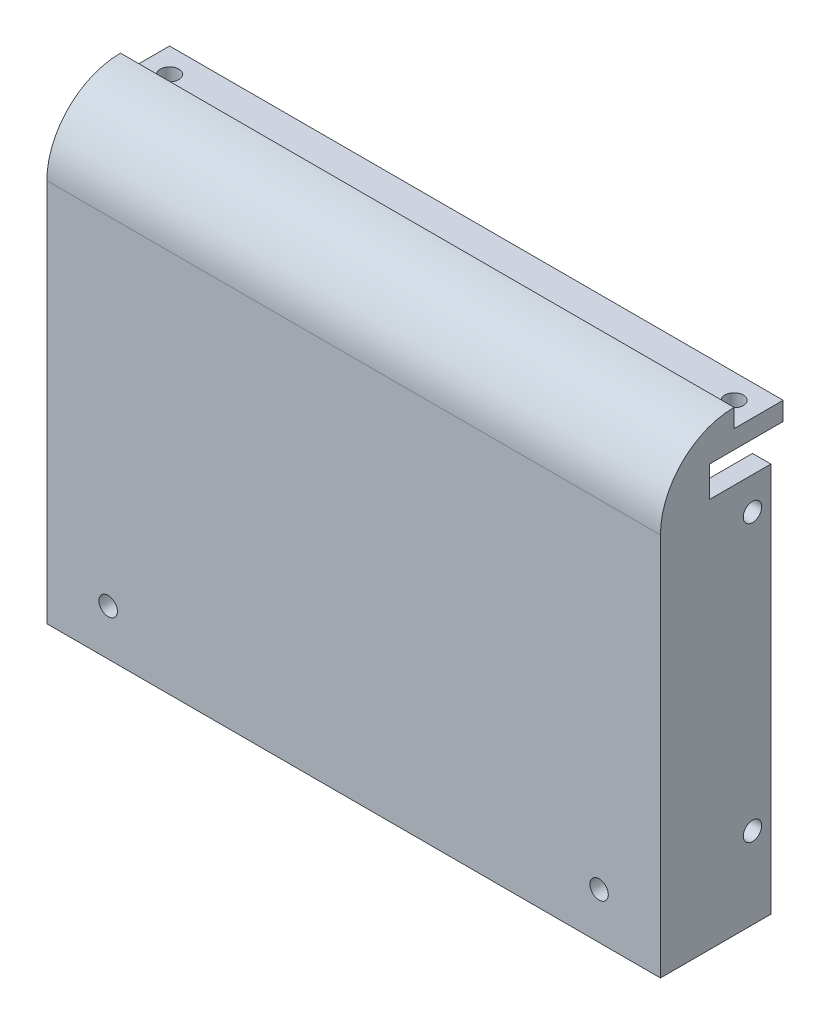
SolidWorks part; units mm, degrees
ref_plane "Front Plane" through (0, 0, 0) normal (0, 0, 1) x (1, 0, 0)
ref_plane "Top Plane" through (0, 0, 0) normal (0, 1, 0) x (1, 0, 0)
ref_plane "Right Plane" through (0, 0, 0) normal (1, 0, 0) x (0, 0, -1)
sketch "Sketch1" plane through (0, 0, 0) normal (0, 1, 0) x (1, 0, 0)
  line L1 (-50, -10) -> (50, -10)
  line L2 (-50, -10) -> (-50, 10)
  line L3 (-50, 10) -> (50, 10)
  line L4 (50, -10) -> (50, 10)
  line L5 (-50, -10) -> (50, 10) construction
  line L6 (-50, 10) -> (50, -10) construction
  point P0 (0, 0)
  dimension "D1" = 100
  dimension "D2" = 20
extrude "Boss-Extrude1" add sketch "Sketch1" along normal blind 3
sketch "Sketch2" plane through (0, 3, 0) normal (0, 1, 0) x (1, 0, 0)
  line L0 (50, 10) -> (-50, 10) construction
  line L1 (-50, 10) -> (-50, -10) construction
  circle A0 centre (-46, 6) radius 1.5
  dimension "D1" = 3
  dimension "D2" = 4
  dimension "D3" = 4
extrude "Cut-Extrude1" cut sketch "Sketch2" against normal up to next
pattern_linear "LPattern1" count 2 spacing 92 along (1, 0, 0) of "Cut-Extrude1"
sketch "Sketch3" plane through (0, 0, 0) normal (0, -1, 0) x (1, 0, 0)
  line L0 (50, 10) -> (50, -10) construction
  line L1 (-50, 10) -> (50, 10)
  line L2 (-50, 10) -> (-50, 7)
  line L3 (-50, 7) -> (50, 7)
  line L4 (50, 10) -> (50, 7)
  dimension "D1" = 3
extrude "Boss-Extrude2" add sketch "Sketch3" along normal blind 68.54
sketch "Sketch4" plane through (0, 0, 7) normal (0, 0, -1) x (-1, 0, 0)
  line L0 (50, -68.54) -> (50, 0) construction
  line L1 (-50, 0) -> (50, 0)
  line L2 (-50, 0) -> (-50, -5)
  line L3 (-50, -5) -> (50, -5)
  line L4 (50, 0) -> (50, -5)
  dimension "D1" = 5
extrude "Boss-Extrude3" add sketch "Sketch4" along normal blind 5
sketch "Sketch5" plane through (0, 3, 0) normal (0, 1, 0) x (1, 0, 0)
  line L0 (50, -10) -> (50, 10) construction
  line L1 (-50, -10) -> (50, -10)
  line L2 (-50, -10) -> (-50, 2)
  line L3 (-50, 2) -> (50, 2)
  line L4 (50, -10) -> (50, 2)
  dimension "D1" = 12
extrude "Boss-Extrude4" add sketch "Sketch5" along normal blind 3
fillet "Fillet4" radius 12 1 edges at (0, 6, 10)
sketch "Sketch6" plane through (0, 0, 7) normal (0, 0, -1) x (-1, 0, 0)
  line L0 (50, -68.54) -> (-50, -68.54) construction
  line L1 (-50, -5) -> (-47, -5)
  line L2 (-50, -5) -> (-50, -68.54)
  line L3 (-50, -68.54) -> (-47, -68.54)
  line L4 (-47, -5) -> (-47, -68.54)
  dimension "D1" = 3
extrude "Boss-Extrude5" add sketch "Sketch6" along normal blind 15
sketch "Sketch7" plane through (50, 0, 0) normal (1, 0, 0) x (0, 0, -1)
  line L0 (8, -5) -> (-2, -5) construction
  line L1 (-10, -6) -> (-10, -68.54) construction
  circle A0 centre (5, -10.27) radius 1.5
  circle A1 centre (5, -55.27) radius 1.5
  dimension "D1" = 3
  dimension "D2" = 3
  dimension "D3" = 45
  dimension "D4" = 5.27
  dimension "D5" = 15
extrude "Cut-Extrude2" cut sketch "Sketch7" against normal up to next
sketch "Sketch8" plane through (0, 0, 10) normal (0, 0, 1) x (1, 0, 0)
  line L0 (50, -68.54) -> (-50, -68.54) construction
  line L1 (-50, -6) -> (-50, -68.54) construction
  circle A0 centre (-40, -61.04) radius 1.5
  dimension "D1" = 3
  dimension "D2" = 7.5
  dimension "D3" = 10
extrude "Cut-Extrude3" cut sketch "Sketch8" against normal up to next
pattern_linear "LPattern2" count 2 spacing 80 along (1, 0, 0) of "Cut-Extrude3"
